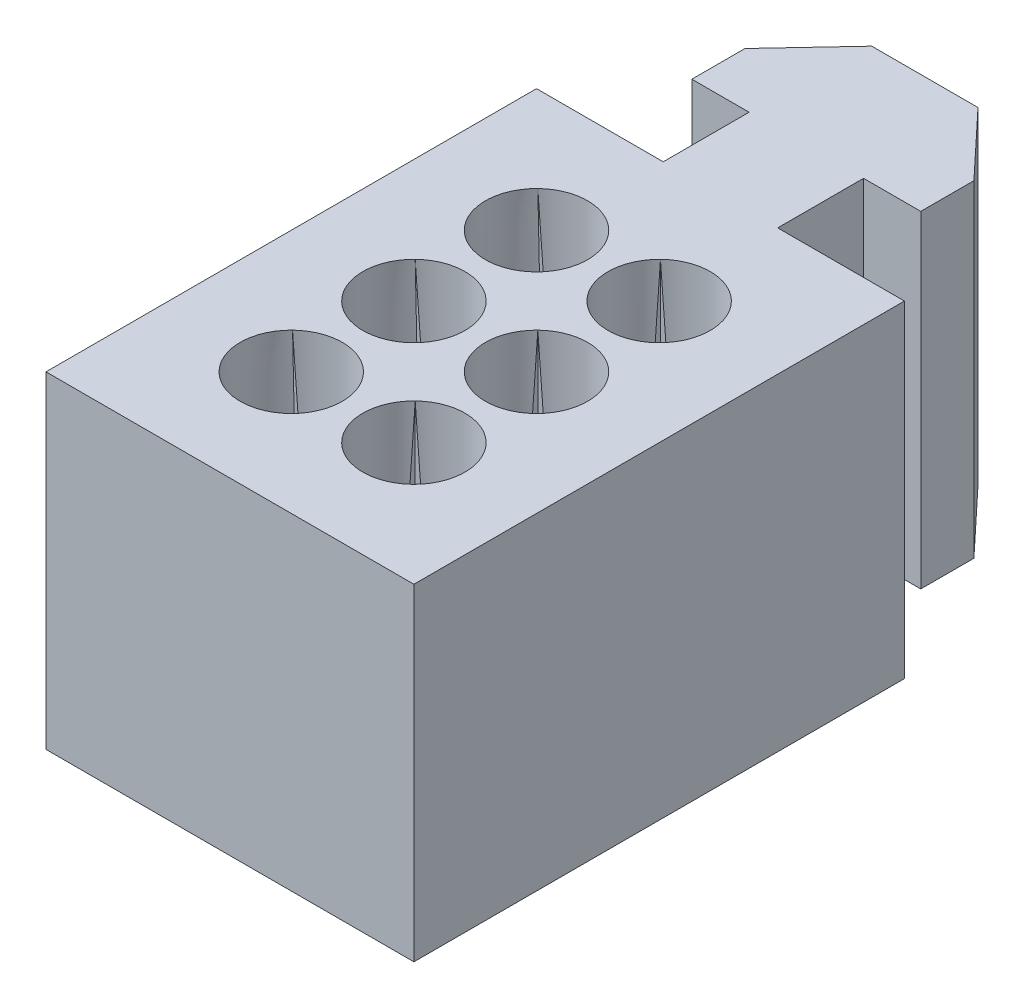
SolidWorks part; units mm, degrees
ref_plane "Спереди" through (0, 0, 0) normal (0, 0, 1) x (1, 0, 0)
ref_plane "Сверху" through (0, 0, 0) normal (0, 1, 0) x (1, 0, 0)
ref_plane "Справа" through (0, 0, 0) normal (1, 0, 0) x (0, 0, -1)
sketch "Эскиз1" plane through (0, 0, 0) normal (0, 1, 0) x (1, 0, 0)
  line L0 (0, 0) -> (0, -3) construction
  line L1 (0, -3) -> (-3, -3) construction
  line L3 (-3, -3) -> (6, -3)
  line L4 (-3, -3) -> (-3, 9)
  line L5 (-3, 9) -> (6, 9)
  line L6 (6, -3) -> (6, 9)
  circle A0 centre (0, 0) radius 1.25
  circle A1 centre (3, 0) radius 1.25
  circle A2 centre (3, 3) radius 1.25
  circle A3 centre (3, 6) radius 1.25
  circle A4 centre (0, 3) radius 1.25
  circle A5 centre (0, 6) radius 1.25
  dimension "D1" = 2.5
  dimension "D4" = 3
  dimension "D5" = 3
  dimension "D6" = 12
  dimension "D7" = 9
  dimension "D8" = 3
  dimension "D9" = 3
  dimension "D2" = 2
  dimension "D3" = 3
extrude "Бобышка-Вытянуть1" add sketch "Эскиз1" along normal blind 10
chamfer "Фаска1" distance 2 angle 38 6 edges at (0, 0, -4.75) (0, 0, -1.75) (0, 0, 1.25) (3, 0, -4.75) (3, 0, -1.75) (3, 0, 1.25) first distance on face at (0, 10, -4.75) first distance on face at (0, 10, -1.75) first distance on face at (0, 10, 1.25) first distance on face at (3, 10, -4.75) first distance on face at (3, 10, -1.75) first distance on face at (3, 10, 1.25)
sketch "Эскиз2" plane through (0, 0, 0) normal (0, 1, 0) x (1, 0, 0)
  line L0 (1.5, 9) -> (1.5, 14) construction
  line L1 (6, 9) -> (-3, 9) construction
  line L2 (-3, 9) -> (0.1, 9) construction
  line L3 (0.1, 9) -> (0.1, 11.1)
  line L4 (0.1, 11.1) -> (-1.3, 11.1)
  line L5 (-1.3, 11.1) -> (-1.3, 12.4)
  line L6 (-1.3, 12.4) -> (0.2, 14)
  line L7 (0.2, 14) -> (2.8, 14)
  line L8 (0.1, 9) -> (2.9, 9)
  line L9 (4.3, 12.4) -> (2.8, 14)
  line L10 (4.3, 11.1) -> (4.3, 12.4)
  line L11 (2.9, 11.1) -> (4.3, 11.1)
  line L12 (2.9, 9) -> (2.9, 11.1)
  dimension "D1" = 5
  dimension "D2" = 3.1
  dimension "D3" = 2.1
  dimension "D4" = 1.4
  dimension "D5" = 1.3
  dimension "D6" = 1.3
extrude "Бобышка-Вытянуть2" add sketch "Эскиз2" along normal blind 8 contours L6 L7 L9 L10 L11 L12 L8 L3 L4 L5
sketch "Эскиз3" plane through (0, 8, 0) normal (0, 1, 0) x (1, 0, 0)
  line L0 (0.8679, 6.8996) -> (0.8679, 5.1004)
  line L1 (1.5, 14) -> (1.5, 11.3074) construction
  line L2 (0.2, 14) -> (2.8, 14) construction
  line L3 (0.8679, 5.1004) -> (-0.8679, 5.1004)
  line L4 (0.8679, 6.8996) -> (-0.8679, 6.8996)
  line L5 (2.1321, 6.8996) -> (3.8679, 6.8996)
  line L6 (2.1321, 5.1004) -> (3.8679, 5.1004)
  line L7 (2.1321, 6.8996) -> (2.1321, 5.1004)
  line L8 (0.8679, 3.8996) -> (-0.8679, 3.8996)
  line L9 (0.8679, 2.1004) -> (-0.8679, 2.1004)
  line L10 (0.8679, 3.8996) -> (0.8679, 2.1004)
  line L11 (2.1321, 3.8996) -> (2.1321, 2.1004)
  line L12 (2.1321, 2.1004) -> (3.8679, 2.1004)
  line L13 (2.1321, 3.8996) -> (3.8679, 3.8996)
  line L14 (0.8679, 0.8996) -> (-0.8679, 0.8996)
  line L15 (0.8679, -0.8996) -> (-0.8679, -0.8996)
  line L16 (0.8679, 0.8996) -> (0.8679, -0.8996)
  line L17 (2.1321, 0.8996) -> (2.1321, -0.8996)
  line L18 (2.1321, -0.8996) -> (3.8679, -0.8996)
  line L19 (2.1321, 0.8996) -> (3.8679, 0.8996)
  arc A0 (-0.8679, 6.8996) -> (-0.8679, 5.1004) centre (0, 6) ccw
  arc A1 (3.8679, 6.8996) -> (3.8679, 5.1004) centre (3, 6) cw
  arc A2 (-0.8679, 3.8996) -> (-0.8679, 2.1004) centre (0, 3) ccw
  arc A3 (3.8679, 3.8996) -> (3.8679, 2.1004) centre (3, 3) cw
  arc A4 (-0.8679, 0.8996) -> (-0.8679, -0.8996) centre (0, 0) ccw
  arc A5 (3.8679, 0.8996) -> (3.8679, -0.8996) centre (3, 0) cw
  dimension "D1" = 3
extrude "Вырез-Вытянуть2" cut sketch "Эскиз3" against normal blind 10 draft 2 draft outward yes
sketch "Эскиз4" plane through (0, 8, 0) normal (0, 1, 0) x (1, 0, 0)
  line L1 (-4.9589, 13.9599) -> (9.6559, 13.9599)
  line L2 (-4.9589, 13.9599) -> (-4.9589, -4.5809)
  line L3 (-4.9589, -4.5809) -> (9.6559, -4.5809)
  line L4 (9.6559, 13.9599) -> (9.6559, -4.5809)
extrude "Вырез-Вытянуть3" cut sketch "Эскиз4" along normal through all
